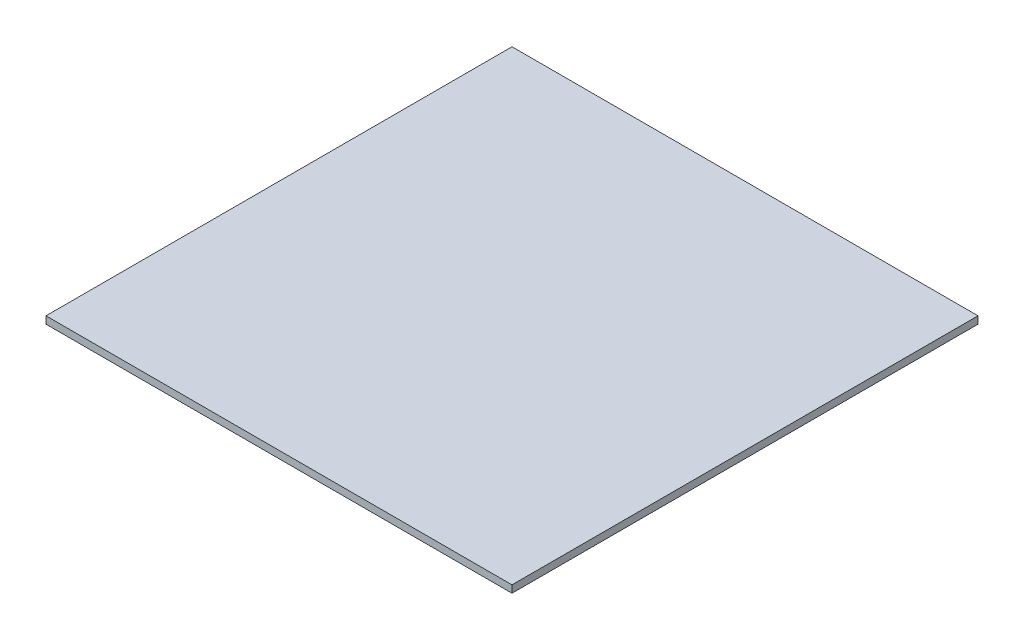
SolidWorks part; units mm, degrees
material "Cedar"
ref_plane "Front Plane" through (0, 0, 0) normal (0, 0, 1) x (1, 0, 0)
ref_plane "Top Plane" through (0, 0, 0) normal (0, 1, 0) x (1, 0, 0)
ref_plane "Right Plane" through (0, 0, 0) normal (1, 0, 0) x (0, 0, -1)
sketch "Sketch1" plane through (0, 0, 0) normal (0, 1, 0) x (1, 0, 0)
  line L1 (-609.6, 609.6) -> (609.6, 609.6)
  line L2 (-609.6, 609.6) -> (-609.6, -609.6)
  line L3 (-609.6, -609.6) -> (609.6, -609.6)
  line L4 (609.6, 609.6) -> (609.6, -609.6)
  line L5 (-609.6, 609.6) -> (609.6, -609.6) construction
  line L6 (-609.6, -609.6) -> (609.6, 609.6) construction
  point P0 (0, 0)
  dimension "D1" = 1219.2
  dimension "D2" = 1219.2
extrude "Boss-Extrude1" add sketch "Sketch1" along normal blind 19.05
